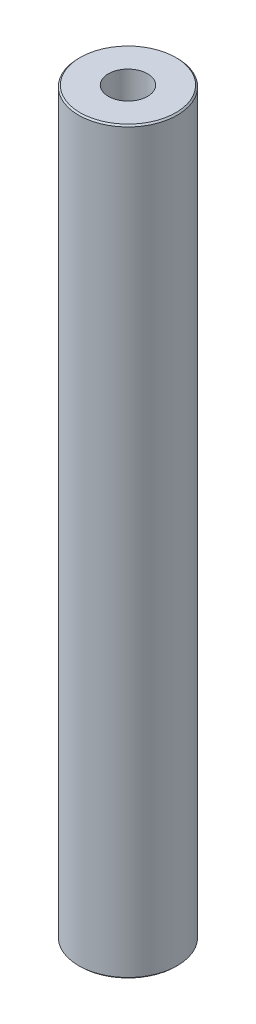
SolidWorks part; units mm, degrees
ref_plane "Front Plane" through (0, 0, 0) normal (0, 0, 1) x (1, 0, 0)
ref_plane "Top Plane" through (0, 0, 0) normal (0, 1, 0) x (1, 0, 0)
ref_plane "Right Plane" through (0, 0, 0) normal (1, 0, 0) x (0, 0, -1)
sketch "Sketch1" plane through (0, 0, 0) normal (0, 1, 0) x (1, 0, 0)
  circle A0 centre (0, 0) radius 40
  dimension "SHAFT_OD" = 80
extrude "Boss-Extrude1" add sketch "Sketch1" along normal blind 600
sketch "Sketch2" plane through (0, 0, 0) normal (0, 1, 0) x (1, 0, 0)
  circle A0 centre (0, 0) radius 15.9205
  dimension "BORE_D" = 31.8409
extrude "Cut-Extrude1" cut sketch "Sketch2" along normal through all
chamfer "Chamfer1" distance 1.1788 angle 45 2 edges at (0, 600, 40) (0, 0, 40)
